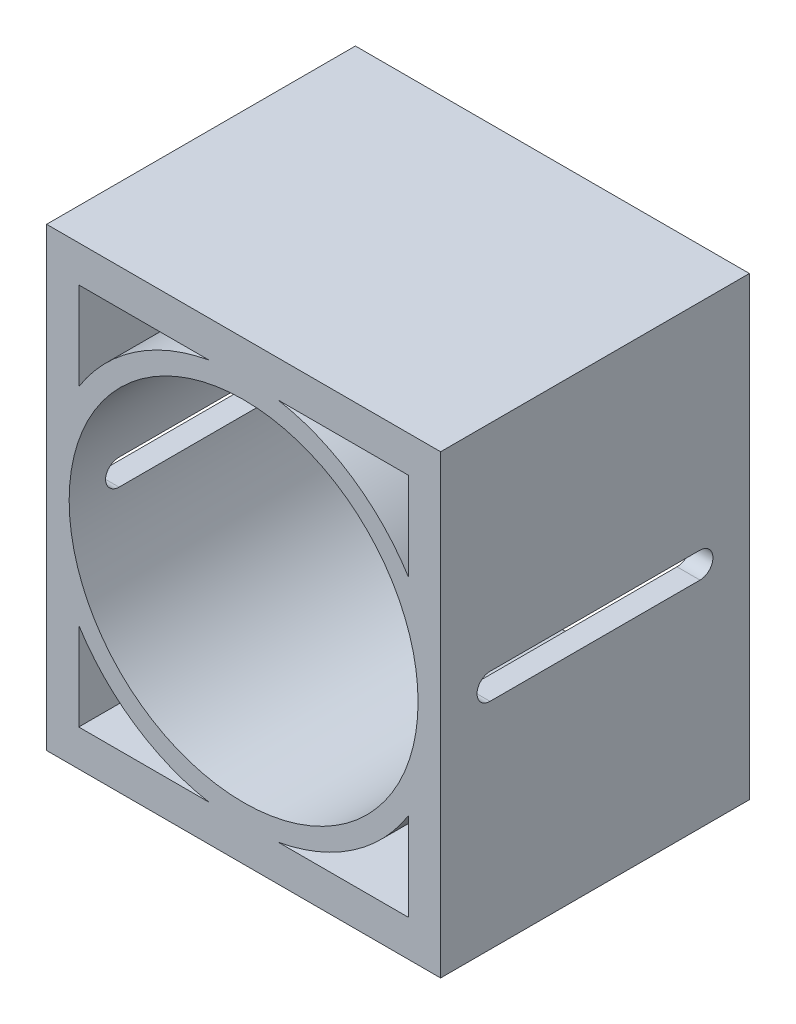
SolidWorks part; units mm, degrees
ref_plane "Front Plane" through (0, 0, 0) normal (0, 0, 1) x (1, 0, 0)
ref_plane "Top Plane" through (0, 0, 0) normal (0, 1, 0) x (1, 0, 0)
ref_plane "Right Plane" through (0, 0, 0) normal (1, 0, 0) x (0, 0, -1)
sketch "Sketch1" plane through (0, 0, 0) normal (0, 0, 1) x (1, 0, 0)
  line L0 (-26.6944, -16.7229) -> (-26.6944, -31)
  line L5 (5.5902, -31) -> (26.6944, -31)
  line L6 (5.5902, 31) -> (26.6944, 31)
  line L7 (-26.6944, 31) -> (-5.5902, 31)
  line L8 (-26.6944, 31) -> (-26.6944, 16.7229)
  line L9 (-26.6944, -31) -> (-5.5902, -31)
  line L10 (26.6944, 31) -> (26.6944, 16.7229)
  line L12 (-26.6944, -31) -> (26.6944, 31) construction
  line L13 (26.6944, -16.7229) -> (26.6944, -31)
  line L21 (-31.9, 36.9) -> (31.9, 36.9)
  line L22 (-31.9, 36.9) -> (-31.9, -36.9)
  line L23 (-31.9, -36.9) -> (31.9, -36.9)
  line L24 (31.9, 36.9) -> (31.9, -36.9)
  line L25 (-31.9, 36.9) -> (31.9, -36.9) construction
  line L26 (-31.9, -36.9) -> (31.9, 36.9) construction
  circle A0 centre (0, 0) radius 28.25
  arc A1 (26.6944, 16.7229) -> (5.5902, 31) centre (0, 0) ccw
  arc A2 (-26.6944, -16.7229) -> (-5.5902, -31) centre (0, 0) ccw
  arc A3 (5.5902, -31) -> (26.6944, -16.7229) centre (0, 0) ccw
  arc A4 (-5.5902, 31) -> (-26.6944, 16.7229) centre (0, 0) ccw
  point P0 (0, 0)
  dimension "D3" = 31.5
  dimension "D4" = 56.5
  dimension "D5" = 73.8
  dimension "D6" = 63.8
extrude "Boss-Extrude19" add sketch "Sketch1" along normal blind 10 contours A0 A3 L13 L9 L0 A2 A4 L8 L7 L10 A1 region at (0, 35.9245, 0)
sketch "Sketch4" plane through (-31.9, 0, 0) normal (-1, 0, 0) x (0, 0, 1)
sketch "Sketch5" plane through (0, 0, 10) normal (0, 0, 1) x (1, 0, 0)
extrude "Boss-Extrude20" add sketch "Sketch1<16>" along normal blind 50
sketch "Sketch1<16>" plane through (0, 0, 0) normal (0, 0, 1) x (1, 0, 0) same geometry as "Sketch1"
ref_plane "Plane4" through (40, 0, 0) normal (1, 0, 0) x (0, 0, -1)
sketch "Sketch7" plane through (40, 0, 0) normal (1, 0, 0) x (0, 0, -1)
  line L0 (5.5, 0) -> (-5.5, 0) construction
  line L1 (-42, 0) -> (-50, 0) construction
  line L2 (-50, -36.9) -> (-50, 36.9) construction
  line L3 (-8, 0) -> (0, 0) construction
  line L4 (-42, 2.1) -> (-8, 2.1)
  line L5 (-42, -2.1) -> (-8, -2.1)
  arc A0 (-42, 2.1) -> (-42, -2.1) centre (-42, 0) ccw
  arc A1 (-8, -2.1) -> (-8, 2.1) centre (-8, 0) ccw
  dimension "D1" = 8
  dimension "D2" = 4.2
  dimension "D3" = 8
extrude "Cut-Extrude1" cut sketch "Sketch7" against normal blind 100
